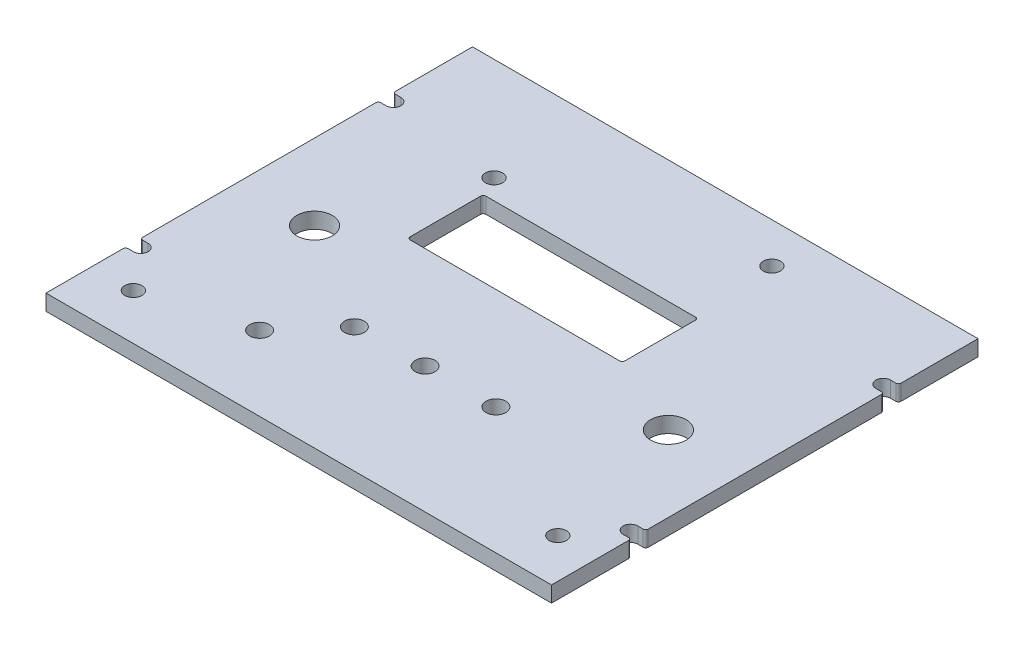
SolidWorks part; units mm, degrees
ref_plane "Front Plane" through (0, 0, 0) normal (0, 0, 1) x (1, 0, 0)
ref_plane "Top Plane" through (0, 0, 0) normal (0, 1, 0) x (1, 0, 0)
ref_plane "Right Plane" through (0, 0, 0) normal (1, 0, 0) x (0, 0, -1)
sketch "Sketch1" plane through (0, 0, 0) normal (0, 1, 0) x (1, 0, 0)
  line L1 (-50.8, -42.8625) -> (50.8, -42.8625)
  line L2 (-50.8, -42.8625) -> (-50.8, 42.8625)
  line L3 (-50.8, 42.8625) -> (50.8, 42.8625)
  line L4 (50.8, -42.8625) -> (50.8, 42.8625)
  line L5 (-50.8, -42.8625) -> (50.8, 42.8625) construction
  line L6 (-50.8, 42.8625) -> (50.8, -42.8625) construction
  point P0 (0, 0)
  dimension "D1" = 101.6
  dimension "D2" = 85.725
extrude "Boss-Extrude1" add sketch "Sketch1" along normal blind 3.175
hole_wizard "#29 (0.136) Diameter Hole1" positions "Sketch2" profile "Sketch3" hole size "#29" standard "ANSI Inch" end condition through all
sketch "Sketch2" plane through (0, 3.175, 0) normal (0, 1, 0) x (1, 0, 0)
  point P0 (-25.8318, 22.2123)
  point P3 (17.4498, 34.7853)
  point P6 (42.8498, -33.6423)
  point P9 (-42.4688, -33.6423)
sketch "Sketch3" plane through (-25.8318, 3.175, -22.2123) normal (1, 0, 0) x (0, 0, 1)
  line L0 (0, 0) -> (0, 3.175)
  line L1 (0, 3.175) -> (1.7272, 3.175)
  line L2 (1.7272, 3.175) -> (1.7272, 0)
  line L5 (1.7272, 0) -> (0, 0)
  line L11 (0, -6.35) -> (0, 107.95) construction
  dimension "Thru Hole Dia." = 3.4544
  dimension "Thru Hole Depth" = 3.175
hole_wizard "9/32 (0.28125) Diameter Hole1" positions "Sketch4" profile "Sketch5" hole size "9/32" standard "ANSI Inch" end condition through all
sketch "Sketch4" plane through (0, 3.175, 0) normal (0, 1, 0) x (1, 0, 0)
  point P0 (-35.56, -4.1275)
  point P3 (35.56, -4.1275)
sketch "Sketch5" plane through (-35.56, 3.175, 4.1275) normal (1, 0, 0) x (0, 0, 1)
  line L0 (0, 0) -> (0, 3.175)
  line L1 (0, 3.175) -> (3.5719, 3.175)
  line L2 (3.5719, 3.175) -> (3.5719, 0)
  line L5 (3.5719, 0) -> (0, 0)
  line L11 (0, -6.35) -> (0, 107.95) construction
  dimension "Thru Hole Dia." = 7.1437
  dimension "Thru Hole Depth" = 3.175
hole_wizard "5/32 (0.15625) Diameter Hole1" positions "Sketch6" profile "Sketch7" hole size "5/32" standard "ANSI Inch" end condition through all
sketch "Sketch6" plane through (0, 3.175, 0) normal (0, 1, 0) x (1, 0, 0)
  point P0 (-22.86, -27.8765)
  point P3 (-13.9422, -17.7443)
  point P6 (0, -17.4625)
  point P9 (14.224, -17.4625)
sketch "Sketch7" plane through (-22.86, 3.175, 27.8765) normal (1, 0, 0) x (0, 0, 1)
  line L0 (0, 0) -> (0, 3.175)
  line L1 (0, 3.175) -> (1.9844, 3.175)
  line L2 (1.9844, 3.175) -> (1.9844, 0)
  line L5 (1.9844, 0) -> (0, 0)
  line L11 (0, -6.35) -> (0, 107.95) construction
  dimension "Thru Hole Dia." = 3.9688
  dimension "Thru Hole Depth" = 3.175
sketch "Sketch8" plane through (0, 3.175, 0) normal (0, 1, 0) x (1, 0, 0)
  line L0 (-24.003, 18.2245) -> (19.177, 18.2245)
  line L5 (19.177, 18.2245) -> (19.177, 2.9845)
  line L6 (-24.003, 2.9845) -> (19.177, 2.9845)
  line L7 (-24.003, 18.2245) -> (-24.003, 2.9845)
  circle A0 centre (-25.8318, 22.2123) radius 1.7272 construction
  dimension "D1" = 1.8288
  dimension "D2" = 45.0088
  dimension "D3" = 3.9878
  dimension "D4" = 19.2278
extrude "Cut-Extrude1" cut sketch "Sketch8" against normal through all
sketch "Sketch9" plane through (0, 3.175, 0) normal (0, 1, 0) x (1, 0, 0)
  line L0 (-50.8, 42.8625) -> (50.8, -42.8625) construction
  line L1 (50.8, 42.8625) -> (-50.8, 42.8625) construction
  line L2 (49.2125, -41.275) -> (-49.2125, -41.275) construction
  line L3 (49.2125, -41.275) -> (49.2125, 41.275) construction
  line L4 (49.2125, 41.275) -> (-49.2125, 41.275) construction
  line L5 (-49.2125, -41.275) -> (-49.2125, 41.275) construction
  line L6 (49.2125, -41.275) -> (-49.2125, 41.275) construction
  line L7 (49.2125, 41.275) -> (-49.2125, -41.275) construction
  line L8 (-50.8, 42.8625) -> (-50.8, -42.8625) construction
  line L9 (-49.2125, 26.8732) -> (-50.8, 26.8732)
  line L10 (-49.2125, 23.9268) -> (-50.8, 23.9268)
  line L11 (-50.8, 26.8732) -> (-50.8, 23.9268)
  line L12 (-49.2125, -23.9268) -> (-50.8, -23.9268)
  line L13 (-50.8, -23.9268) -> (-50.8, -26.8732)
  line L14 (-49.2125, -26.8732) -> (-50.8, -26.8732)
  line L15 (0, 0) -> (0, 12.7264) construction
  line L16 (49.2125, -26.8732) -> (50.8, -26.8732)
  line L17 (50.8, -23.9268) -> (50.8, -26.8732)
  line L18 (49.2125, -23.9268) -> (50.8, -23.9268)
  line L19 (50.8, 26.8732) -> (50.8, 23.9268)
  line L20 (49.2125, 23.9268) -> (50.8, 23.9268)
  line L21 (49.2125, 26.8732) -> (50.8, 26.8732)
  arc A0 (-49.2125, 23.9268) -> (-49.2125, 26.8732) centre (-49.2125, 25.4) ccw
  arc A1 (-49.2125, -26.8732) -> (-49.2125, -23.9268) centre (-49.2125, -25.4) ccw
  arc A2 (49.2125, -26.8732) -> (49.2125, -23.9268) centre (49.2125, -25.4) cw
  arc A3 (49.2125, 23.9268) -> (49.2125, 26.8732) centre (49.2125, 25.4) cw
  point P4 (0, 0)
  point P16 (-49.2125, 0)
  dimension "D3" = 25.4
  dimension "D5" = 1.4732
  dimension "D1" = 1.5875
  dimension "D2" = 1.5875
  dimension "D4" = 2
extrude "Cut-Extrude2" cut sketch "Sketch9" against normal through all
fillet "Fillet1" radius 0.508 12 edges at (50.8, 1.5875, -23.9268) (50.8, 1.5875, -26.8732) (50.8, 1.5875, 23.9268) (50.8, 1.5875, 26.8732) (-50.8, 1.5875, 23.9268) (-50.8, 1.5875, 26.8732) (-50.8, 1.5875, -23.9268) (-50.8, 1.5875, -26.8732) (-24.003, 1.5875, -2.9845) (19.177, 1.5875, -2.9845) (19.177, 1.5875, -18.2245) (-24.003, 1.5875, -18.2245)
